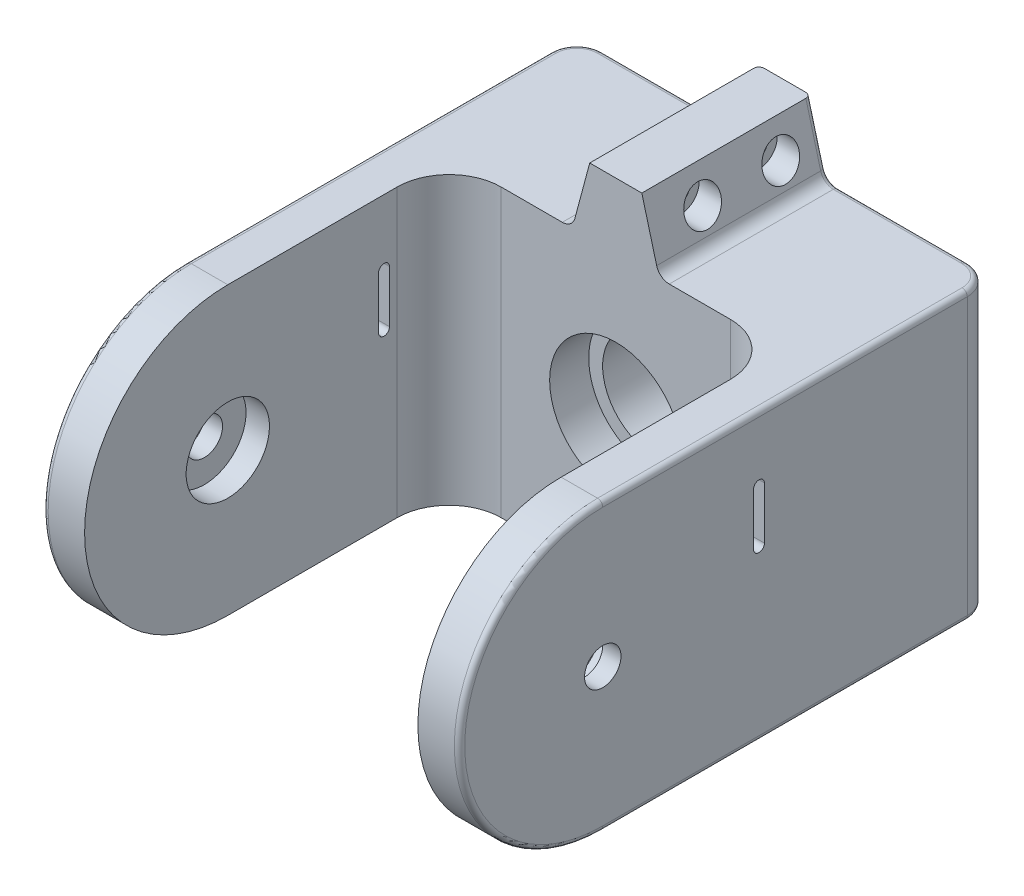
SolidWorks part; units mm, degrees
ref_plane "Front Plane" through (0, 0, 0) normal (0, 0, 1) x (1, 0, 0)
ref_plane "Top Plane" through (0, 0, 0) normal (0, 1, 0) x (1, 0, 0)
ref_plane "Right Plane" through (0, 0, 0) normal (1, 0, 0) x (0, 0, -1)
sketch "Sketch1" plane through (0, 0, 0) normal (0, 0, 1) x (1, 0, 0)
  circle A2 centre (0, 0) radius 25.4
  circle A3 centre (0, 0) radius 25.4 construction
  circle A4 centre (0, 0) radius 20.05
  circle A5 centre (0, 0) radius 19.05 construction
  dimension "D1" = 1
extrude "Centre Hole for L2" add sketch "Sketch1" along normal blind 30 contours A4 | A2
sketch "Sketch2" plane through (0, 0, 30) normal (0, 0, 1) x (1, 0, 0)
  line L0 (0, 48.4974) -> (0, 0) construction
  line L5 (-80, 55) -> (-80, -55)
  line L12 (0, 0) -> (72.986, 0) construction
  line L16 (-80, 55) -> (80, 55)
  line L17 (80, 55) -> (80, -55)
  line L18 (-80, -55) -> (80, -55)
  circle A0 centre (0, 0) radius 25.4
  circle A1 centre (0, 0) radius 25.4 construction
  circle A5 centre (0, 0) radius 25.4
  point P13 (0, 55)
  dimension "D1" = 80
  dimension "D2" = 110
extrude "Main Structure" add sketch "Sketch2" along normal blind 100 and the other way blind 50 separate body contours L5 L18 L17 L16 | A5
sketch "Sketch3" plane through (-80, 0, 0) normal (-1, 0, 0) x (0, 0, 1)
  line L0 (130, 55) -> (130, -55) construction
  line L1 (130, 55) -> (130, -55)
  line L2 (-20, 55) -> (130, 55) construction
  arc A0 (130, 55) -> (130, -55) centre (130, 0) cw
extrude "Bearing Curve" add sketch "Sketch3" against normal blind 16 contours A0 L1
mirror "Upright Mirror" about plane through (0, 0, 0) normal (1, 0, 0) of "Bearing Curve"
sketch "Sketch6" plane through (-80, 0, 0) normal (-1, 0, 0) x (0, 0, 1)
  circle A0 centre (130, 0) radius 7
  dimension "D1" = 14
extrude "Shaft Hole" cut sketch "Sketch6" against normal up to surface (16 mm away) up to face at (-64, 0, 157.5)
sketch "Sketch4" plane through (0, 55, 0) normal (0, 1, 0) x (1, 0, 0)
  line L0 (0, -110) -> (0, 20) construction
  line L1 (-64, -130) -> (64, -130) construction
  line L2 (-80, 20) -> (80, 20) construction
  line L3 (-64, -130) -> (-64, -65)
  line L4 (-44, -45) -> (44, -45)
  line L5 (-64, -130) -> (64, -130)
  line L6 (64, -130) -> (64, -65)
  arc A0 (-64, -65) -> (-44, -45) centre (-44, -65) cw
  arc A1 (64, -65) -> (44, -45) centre (44, -65) ccw
  point P17 (0, -130)
  point P20 (0, -45)
  dimension "D2" = 20
  dimension "D1" = 65
extrude "Wrist Cutout" cut sketch "Sketch4" against normal through all
sketch "Sketch9" plane through (-64, 0, 0) normal (1, 0, 0) x (0, 0, -1)
  circle A0 centre (-130, 0) radius 16
  dimension "D1" = 32
extrude "Bearing" cut sketch "Sketch9" against normal blind 9
mirror "Bearing Mirror" about plane through (0, 0, 0) normal (1, 0, 0) of "Shaft Hole", "Bearing"
fillet "Fillet2" radius 10 2 edges at (-80, 0, -20) (80, 0, -20)
sketch "Sketch10" plane through (0, 0, -20) normal (0, 0, -1) x (-1, 0, 0)
  line L0 (0, 55) -> (0, 80) construction
  line L1 (70, 55) -> (-70, 55) construction
  line L2 (10, 80) -> (-10, 80)
  line L3 (-10, 80) -> (-16.6987, 55)
  line L4 (-16.6987, 55) -> (16.6987, 55)
  line L5 (10, 80) -> (16.6987, 55)
  dimension "D1" = 25
  dimension "D2" = 10
  dimension "D3" = 75
extrude "Bolt Structure" add sketch "Sketch10" against normal up to surface (65 mm away) up to face at (0, 0, 45)
sketch "Sketch11" plane through (0, 0, 0) normal (1, 0, 0) x (0, 0, -1)
  line L1 (-45, 67.5) -> (20, 67.5) construction
  line L2 (-45, 55) -> (-45, 80) construction
  line L3 (20, 80) -> (20, 55) construction
  circle A1 centre (5, 67.5) radius 3.1
  circle A2 centre (-25, 67.5) radius 3.1
  dimension "D1" = 6.2
  dimension "D2" = 15
  dimension "D3" = 30
extrude "Cut-Extrude6" cut sketch "Sketch11" against normal through all both and the other way through all
sketch "Sketch13" plane through (0, 0, 0) normal (1, 0, 0) x (0, 0, -1)
  circle A0 centre (5, 67.5) radius 7
  circle A1 centre (-25, 67.5) radius 7
  dimension "D1" = 14
extrude "Cut-Extrude8" cut sketch "Sketch13" along normal up to surface (8.3494 mm away) from offset 5 up to face at (14.18, 64.4, -5)
mirror "Mirror8" about plane through (0, 0, 0) normal (0, 1, 0) of "Cut-Extrude6", "Cut-Extrude8", "Bolt Structure"
fillet "Fillet3" radius 5 4 edges at (-16.6987, -55, 12.5) (16.6987, -55, 12.5) (-16.6987, 55, 12.5) (16.6987, 55, 12.5)
fillet "Fillet1" radius 2 22 edges at (-80, 55, 60) (-80, -55, 60) (80, -55, 60) (80, 55, 60) (-80, 0, 185) (-12.8529, -69.353, -20) (-17.4916, -56.0332, -20) (-45.2677, -55, -20) (-77.0711, -55, -17.0711) (-12.8529, 69.353, -20) (-17.4916, 56.0332, -20) (-45.2677, 55, -20) (-77.0711, 55, -17.0711) (12.8529, 69.353, -20) (17.4916, 56.0332, -20) (45.2677, 55, -20) (77.0711, 55, -17.0711) (12.8529, -69.353, -20) (17.4916, -56.0332, -20) (45.2677, -55, -20) (77.0711, -55, -17.0711) (80, 0, 185)
sketch "Sketch14" plane through (-80, 0, 0) normal (-1, 0, 0) x (0, 0, 1)
  line L0 (70, 30) -> (70, 10) construction
  line L1 (72.1, 30) -> (72.1, 10)
  line L2 (67.9, 30) -> (67.9, 10)
  arc A0 (72.1, 30) -> (67.9, 30) centre (70, 30) ccw
  arc A1 (67.9, 10) -> (72.1, 10) centre (70, 10) ccw
  point P2 (70, 20)
  dimension "D1" = 4.2
  dimension "D2" = 20
  dimension "D3" = 10
  dimension "D4" = 70
extrude "Tensioner Slot" cut sketch "Sketch14" against normal up to surface (16 mm away) up to face at (-64, 0, 114)
mirror "Mirror9" about plane through (0, 0, 0) normal (1, 0, 0) of "Tensioner Slot"
